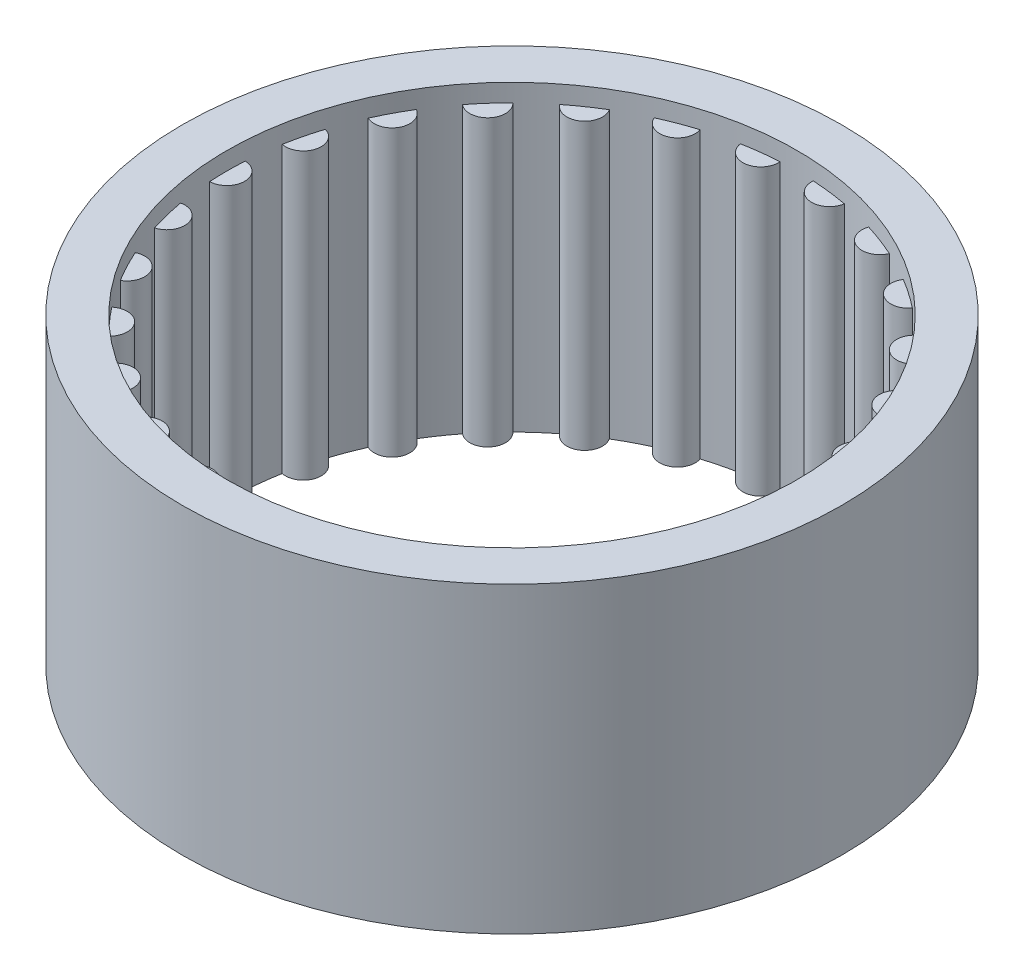
SolidWorks part; units mm, degrees
ref_plane "Front Plane" through (0, 0, 0) normal (0, 0, 1) x (1, 0, 0)
ref_plane "Top Plane" through (0, 0, 0) normal (0, 1, 0) x (1, 0, 0)
ref_plane "Right Plane" through (0, 0, 0) normal (1, 0, 0) x (0, 0, -1)
sketch "Sketch1" plane through (0, 0, 0) normal (0, 1, 0) x (1, 0, 0)
  circle A0 centre (15.5, 0) radius 1
  circle A1 centre (15.0351, -3.8291) radius 1
  circle A2 centre (13.6673, -7.4356) radius 1
  circle A3 centre (11.4762, -10.61) radius 1
  circle A4 centre (8.589, -13.1677) radius 1
  circle A5 centre (5.1737, -14.9603) radius 1
  circle A6 centre (1.4286, -15.8833) radius 1
  circle A7 centre (-2.4286, -15.8833) radius 1
  circle A8 centre (-6.1737, -14.9603) radius 1
  circle A9 centre (-9.589, -13.1677) radius 1
  circle A10 centre (-12.4762, -10.61) radius 1
  circle A11 centre (-14.6673, -7.4356) radius 1
  circle A12 centre (-16.0351, -3.8291) radius 1
  circle A13 centre (-16.5, 0) radius 1
  circle A14 centre (-16.0351, 3.8291) radius 1
  circle A15 centre (-14.6673, 7.4356) radius 1
  circle A16 centre (-12.4762, 10.61) radius 1
  circle A17 centre (-9.589, 13.1677) radius 1
  circle A18 centre (-6.1737, 14.9603) radius 1
  circle A19 centre (-2.4286, 15.8833) radius 1
  circle A20 centre (1.4286, 15.8833) radius 1
  circle A21 centre (5.1737, 14.9603) radius 1
  circle A22 centre (8.589, 13.1677) radius 1
  circle A23 centre (11.4762, 10.61) radius 1
  circle A24 centre (13.6673, 7.4356) radius 1
  circle A25 centre (15.0351, 3.8291) radius 1
  spline S0 degree 4 number of poles 315 (14.4, 0) -> (-15.4, 0) construction
sketch "Sketch2" plane through (0, 0, 0) normal (0, 1, 0) x (1, 0, 0)
  circle A0 centre (15.5, 0) radius 1
  circle A1 centre (15.0351, -3.8291) radius 1
  circle A2 centre (13.6673, -7.4356) radius 1
  circle A3 centre (11.4762, -10.61) radius 1
  circle A4 centre (8.589, -13.1677) radius 1
  circle A5 centre (5.1737, -14.9603) radius 1
  circle A6 centre (1.4286, -15.8833) radius 1
  circle A7 centre (-2.4286, -15.8833) radius 1
  circle A8 centre (-6.1737, -14.9603) radius 1
  circle A9 centre (-9.589, -13.1677) radius 1
  circle A10 centre (-12.4762, -10.61) radius 1
  circle A11 centre (-14.6673, -7.4356) radius 1
  circle A12 centre (-16.0351, -3.8291) radius 1
  circle A13 centre (-16.5, 0) radius 1
  circle A14 centre (-16.0351, 3.8291) radius 1
  circle A15 centre (-14.6673, 7.4356) radius 1
  circle A16 centre (-12.4762, 10.61) radius 1
  circle A17 centre (-9.589, 13.1677) radius 1
  circle A18 centre (-6.1737, 14.9603) radius 1
  circle A19 centre (-2.4286, 15.8833) radius 1
  circle A20 centre (1.4286, 15.8833) radius 1
  circle A21 centre (5.1737, 14.9603) radius 1
  circle A22 centre (8.589, 13.1677) radius 1
  circle A23 centre (11.4762, 10.61) radius 1
  circle A24 centre (13.6673, 7.4356) radius 1
  circle A25 centre (15.0351, 3.8291) radius 1
extrude "Boss-Extrude1" add sketch "Sketch2" along normal blind 8 and the other way blind 8
sketch "Sketch4" plane through (0, 0, 0) normal (0, 1, 0) x (1, 0, 0)
  line L0 (-15.4, 0) -> (14.4, 0) construction
  line L1 (0, 0) -> (0, 14.9128) construction
  line L2 (0, 0) -> (0, -14.9128) construction
  line L3 (0, 0) -> (-0.5, 0) construction
  line L4 (-0.5, 0) -> (-0.5, 15.3103) construction
  line L5 (-0.5, 0) -> (-0.5, -15.3103) construction
  line L6 (14.4, 0) -> (15.5, 0) construction
  line L7 (0, 0) -> (10, 0) construction
  line L8 (7.9, 0) -> (9.5, 0)
  line L9 (-0.5, 0) -> (9.5, 0) construction
  line L10 (-0.5, 15.3103) -> (-0.5, -15.3103) construction
  circle A0 centre (-0.5, 0) radius 16
  circle A1 centre (15.5, 0) radius 1
  circle A2 centre (15.0351, -3.8291) radius 1
  circle A3 centre (13.6673, -7.4356) radius 1
  circle A4 centre (11.4762, -10.61) radius 1
  circle A5 centre (8.589, -13.1677) radius 1
  circle A6 centre (5.1737, -14.9603) radius 1
  circle A7 centre (1.4286, -15.8833) radius 1
  circle A8 centre (-2.4286, -15.8833) radius 1
  circle A9 centre (-6.1737, -14.9603) radius 1
  circle A10 centre (-9.589, -13.1677) radius 1
  circle A11 centre (-12.4762, -10.61) radius 1
  circle A12 centre (-14.6673, -7.4356) radius 1
  circle A13 centre (-16.0351, -3.8291) radius 1
  circle A14 centre (-16.5, 0) radius 1
  circle A15 centre (-16.0351, 3.8291) radius 1
  circle A16 centre (-14.6673, 7.4356) radius 1
  circle A17 centre (-12.4762, 10.61) radius 1
  circle A18 centre (-9.589, 13.1677) radius 1
  circle A19 centre (-6.1737, 14.9603) radius 1
  circle A20 centre (-2.4286, 15.8833) radius 1
  circle A21 centre (1.4286, 15.8833) radius 1
  circle A22 centre (5.1737, 14.9603) radius 1
  circle A23 centre (8.589, 13.1677) radius 1
  circle A24 centre (11.4762, 10.61) radius 1
  circle A25 centre (13.6673, 7.4356) radius 1
  circle A26 centre (15.0351, 3.8291) radius 1
  circle A27 centre (0, 0) radius 10
  circle A28 centre (10, 0) radius 2.1
  circle A29 centre (5, -8.6603) radius 2.1
  circle A30 centre (-5, -8.6603) radius 2.1
  circle A31 centre (-10, 0) radius 2.1
  circle A32 centre (-5, 8.6603) radius 2.1
  circle A33 centre (5, 8.6603) radius 2.1
  circle A34 centre (-6, 8.6603) radius 2.1
  circle A35 centre (4, 8.6603) radius 2.1
  circle A36 centre (9, 0) radius 2.1
  circle A37 centre (4, -8.6603) radius 2.1
  circle A38 centre (-6, -8.6603) radius 2.1
  circle A39 centre (-1, 0) radius 10
  circle A40 centre (-11, 0) radius 2.1
  circle A41 centre (9.5, 0) radius 1.5
  circle A42 centre (4.5, -8.6603) radius 1.5
  circle A43 centre (-5.5, -8.6603) radius 1.5
  circle A44 centre (-10.5, 0) radius 1.5
  circle A45 centre (-5.5, 8.6603) radius 1.5
  circle A46 centre (4.5, 8.6603) radius 1.5
  circle A47 centre (-0.5, 0) radius 19.5
  circle A48 centre (0, 0) radius 5.55
  circle A49 centre (-0.5, 0) radius 5.55
  spline S0 degree 4 number of poles 369 (14.1521, 3.1658) -> (-14.9531, 3.4358) construction
  spline S1 degree 4 number of poles 315 (14.4, 0) -> (-15.4, 0)
  spline S2 degree 4 number of poles 315 (14.4, 0) -> (-15.4, 0)
  spline S3 degree 4 number of poles 315 (-15.4, 0) -> (14.4, 0)
  spline S4 degree 4 number of poles 315 (-15.4, 0) -> (14.4, 0)
  dimension "D1" = 32
  dimension "D2" = 2
  dimension "D4" = 20
  dimension "D5" = 4.2
  dimension "D8" = 6
  dimension "D7" = 10
  dimension "D9" = 10
  dimension "D3" = 26
  dimension "D6" = 6
sketch "Sketch5" plane through (0, 0, 0) normal (0, 1, 0) x (1, 0, 0)
  circle A0 centre (-0.5, 0) radius 16
  circle A1 centre (-0.5, 0) radius 18.5
extrude "Boss-Extrude3" add sketch "Sketch5" along normal blind 8 and the other way blind 8
sketch "Sketch6" plane through (0, 8, 0) normal (0, 1, 0) x (1, 0, 0)
  circle A0 centre (-0.5, 0) radius 18.5 construction
  circle A1 centre (-0.5, 0) radius 18.5
  circle A2 centre (-0.5, 0) radius 16
  dimension "D1" = 37
  dimension "D2" = 32
extrude "Boss-Extrude4" add sketch "Sketch6" along normal blind 1
sketch "Sketch7" plane through (0, 9, 0) normal (0, 1, 0) x (1, 0, 0)
  circle A0 centre (-0.5, 0) radius 18.5 construction
  circle A1 centre (-5.5, -8.6603) radius 1.5 construction
  circle A2 centre (4.5, -8.6603) radius 1.5 construction
  circle A3 centre (9.5, 0) radius 1.5 construction
  circle A4 centre (-10.5, 0) radius 1.5 construction
  circle A5 centre (-5.5, 8.6603) radius 1.5 construction
  circle A6 centre (4.5, 8.6603) radius 1.5 construction
  circle A7 centre (-0.5, 0) radius 18.5
  circle A8 centre (-5.5, -8.6603) radius 1.5
  circle A9 centre (4.5, -8.6603) radius 1.5
  circle A10 centre (9.5, 0) radius 1.5
  circle A11 centre (-10.5, 0) radius 1.5
  circle A12 centre (-5.5, 8.6603) radius 1.5
  circle A13 centre (4.5, 8.6603) radius 1.5
